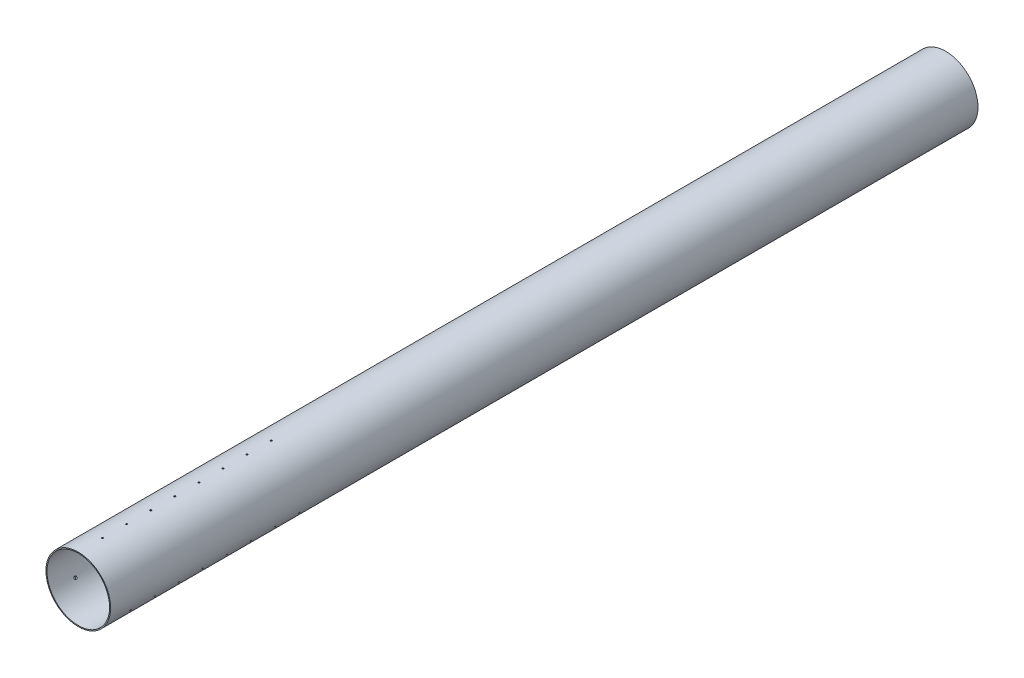
SolidWorks part; units mm, degrees
ref_plane "Front Plane" through (0, 0, 0) normal (0, 0, 1) x (1, 0, 0)
ref_plane "Top Plane" through (0, 0, 0) normal (0, 1, 0) x (1, 0, 0)
ref_plane "Right Plane" through (0, 0, 0) normal (1, 0, 0) x (0, 0, -1)
sketch "Sketch1" plane through (0, 0, 0) normal (0, 0, 1) x (1, 0, 0)
  circle A0 centre (0, 0) radius 51.1175
  circle A1 centre (0, 0) radius 49.53
  dimension "D1" = 102.235
  dimension "D2" = 1.5875
extrude "Boss-Extrude1" add sketch "Sketch1" along normal blind 1371.6
hole_wizard "CSK for #2 Flat Head Machine Screw1" positions "3DSketch1" profile "Sketch2" countersink size "#2" standard "ANSI Inch"
sketch3d "3DSketch1"
  line L1 (0, 57.7215, 1333.2201) -> (0, 51.0596, 1333.2201) construction
  point P0 (0, 49.53, 1333.2201)
sketch "Sketch2" plane through (0, 49.53, 1333.2201) normal (1, 0, 0) x (0, 0, -1)
  line L0 (0, 0) -> (0, 20.2978)
  line L1 (0, 20.2978) -> (1.2192, 20.2978)
  line L2 (1.2192, 20.2978) -> (1.2192, 1.1103)
  line L3 (1.2192, 1.1103) -> (2.1844, 0)
  line L5 (2.1844, 0) -> (0, 0)
  line L6 (-1.2192, 1.1103) -> (-2.1844, 0) construction
  line L11 (0, -6.35) -> (0, 107.95) construction
  dimension "Thru Hole Dia." = 2.4384
  dimension "Thru Hole Depth" = 20.2978
  dimension "Near C'Sink Dia." = 4.3688
  dimension "Near C'Sink Angle" = 82
pattern_linear "LPattern1" count 8 spacing 38.1 along (0, 0, -1) of "CSK for #2 Flat Head Machine Screw1"
pattern_circular "CirPattern1" count 3 over 360 about axis through (0, 0, 1371.6) along (0, 0, 1) of "LPattern1", "CSK for #2 Flat Head Machine Screw1"
